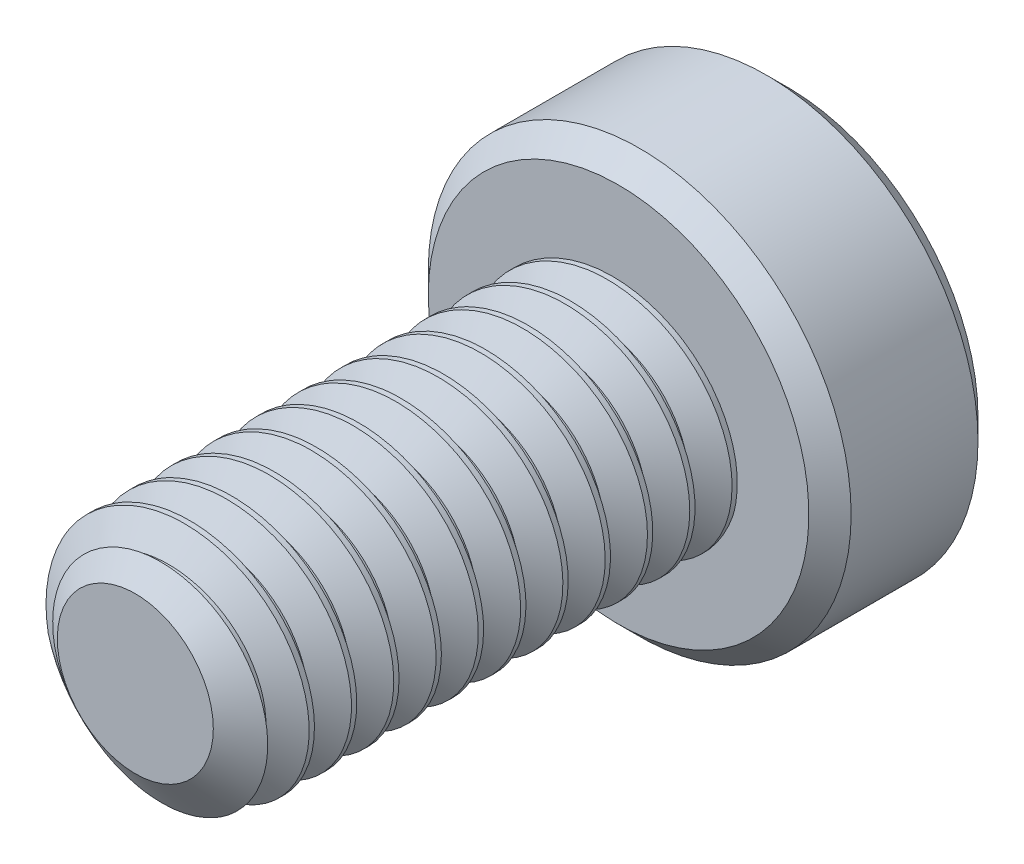
SolidWorks part; units mm, degrees
other "DetailItem1"
ref_plane "Front Plane" through (0, 0, 0) normal (0, 0, 1) x (1, 0, 0)
ref_plane "Top Plane" through (0, 0, 0) normal (0, 1, 0) x (1, 0, 0)
ref_plane "Right Plane" through (0, 0, 0) normal (1, 0, 0) x (0, 0, -1)
sketch "Sketch1" plane through (0, 0, 0) normal (0, 0, 1) x (1, 0, 0)
  circle A0 centre (0, 0) radius 2
  dimension "OD" = 4
extrude "Extrude1" add sketch "Sketch1" against normal blind 8
sketch "Sketch2" plane through (0, 0, 0) normal (0, 0, 1) x (1, 0, 0)
  circle A0 centre (0, 0) radius 2 construction
  circle A1 centre (0, 0) radius 2
curve "Helix/Spiral1" pitch 0.7 height 8.7 radius 2 centre (0, 0, 0) axis (0, 0, -1) start towards (0, 1, 0) parameters "pitch"=0.7
sketch "Sketch3" plane through (0, 0, 0) normal (1, 0, 0) x (0, 0, -1)
  line L0 (-0.6125, 2) -> (-0.35, 1.5453)
  line L1 (-0.35, 1.5453) -> (-0.2625, 1.5453)
  line L2 (-0.2625, 1.5453) -> (0, 2)
  line L3 (-0.6125, 2) -> (0, 2)
  line L4 (-0.3062, 2) -> (-0.3062, 1.5453) construction
  line L5 (-0.4813, 1.7727) -> (-0.1313, 1.7727) construction
  line L6 (0, 2) -> (0, -2) construction
  dimension "D1" = 0.0875
  dimension "D2" = 0.35
  dimension "D3" = 60
sweep "Cut-Sweep1" cut profiles "Sketch3" path "Helix/Spiral1"
sketch "Sketch4" plane through (0, 0, 0) normal (1, 0, 0) x (0, 0, -1)
  line L0 (0.4962, 2) -> (0, 1.2913)
  line L1 (0, 1.2913) -> (0, 2)
  line L2 (0.4962, 2) -> (0, 2)
  line L3 (-0.6125, 2) -> (0, 2) construction
  line L4 (0, 0) -> (7.0209, 0) construction
  dimension "D1" = 55
  dimension "D2" = 0.254
revolve "Cut-Revolve1" cut sketch "Sketch4" angle 360 about L4
sketch "Sketch6" plane through (0, 0, -8) normal (0, 0, -1) x (-1, 0, 0)
  circle A0 centre (0, 0) radius 3.5
  dimension "head dia" = 7
extrude "Extrude2" add sketch "Sketch6" along normal blind 2.8
sketch "Sketch7" plane through (0, 0, -10.8) normal (0, 0, -1) x (-1, 0, 0)
  line L1 (0, 1.4434) -> (-1.25, 0.7217)
  line L2 (-1.25, 0.7217) -> (-1.25, -0.7217)
  line L3 (-1.25, -0.7217) -> (0, -1.4434)
  line L4 (0, -1.4434) -> (1.25, -0.7217)
  line L5 (1.25, -0.7217) -> (1.25, 0.7217)
  line L6 (1.25, 0.7217) -> (0, 1.4434)
  circle A0 centre (0, 0) radius 1.25 construction
  dimension "hex dia" = 2.5
extrude "Cut-Extrude1" cut sketch "Sketch7" against normal blind 1.875
sketch "Sketch8" plane through (0, 0, -10.8) normal (0, 0, -1) x (-1, 0, 0)
  circle A0 centre (0, 0) radius 1.4434
extrude "Cut-Extrude2" cut sketch "Sketch8" against normal through all draft 45
chamfer "Chamfer1" distance 0.35 angle 45 2 edges at (-3.5, 0, -10.8) (-3.5, 0, -8)
sketch "Sketch10" plane through (0, 0, -8) normal (0, 0, 1) x (1, 0, 0)
  circle A1 centre (0, 0) radius 2
  circle A2 centre (0, 0) radius 2
  dimension "D1" = 0
ref_plane "Plane1" through (0, 0, -12) normal (0, 0, 1) x (1, 0, 0)
extrude "partial thread" [suppressed] add sketch "Sketch10" along normal up to surface (8 mm away) separate body up to plane "Plane1"
chamfer "Chamfer2" [suppressed] distance 0.08 angle 45
combine bodies "Combine1" [suppressed] operation type add bodies to combine 107 108
sketch "Sketch9" plane through (0, 0, 0) normal (1, 0, 0) x (0, 0, -1)
  line L0 (0, 2) -> (0, -2) construction
  line L1 (1.75, 2) -> (1.75, -2) construction
  dimension "D1" = 1.75
equation "\"D3@Helix/Spiral1\" = \"screw length@Extrude1\"+\"pitch@Helix/Spiral1\""
equation "\"D1@Sketch3\" = \"pitch@Helix/Spiral1\"*.125"
equation "\"D2@Sketch3\" = \"pitch@Helix/Spiral1\"*.5"
equation "\"D1@Cut-Extrude1\" = \"hex dia@Sketch7\"*.75"
equation "\"D1@Chamfer1\" = \"head dia@Sketch6\"*.05"
equation "\"D1@Sketch9\" = \"pitch@Helix/Spiral1\"*2.5"
equation "\"D1@Chamfer2\"=\"OD@Sketch1\"*.02"
